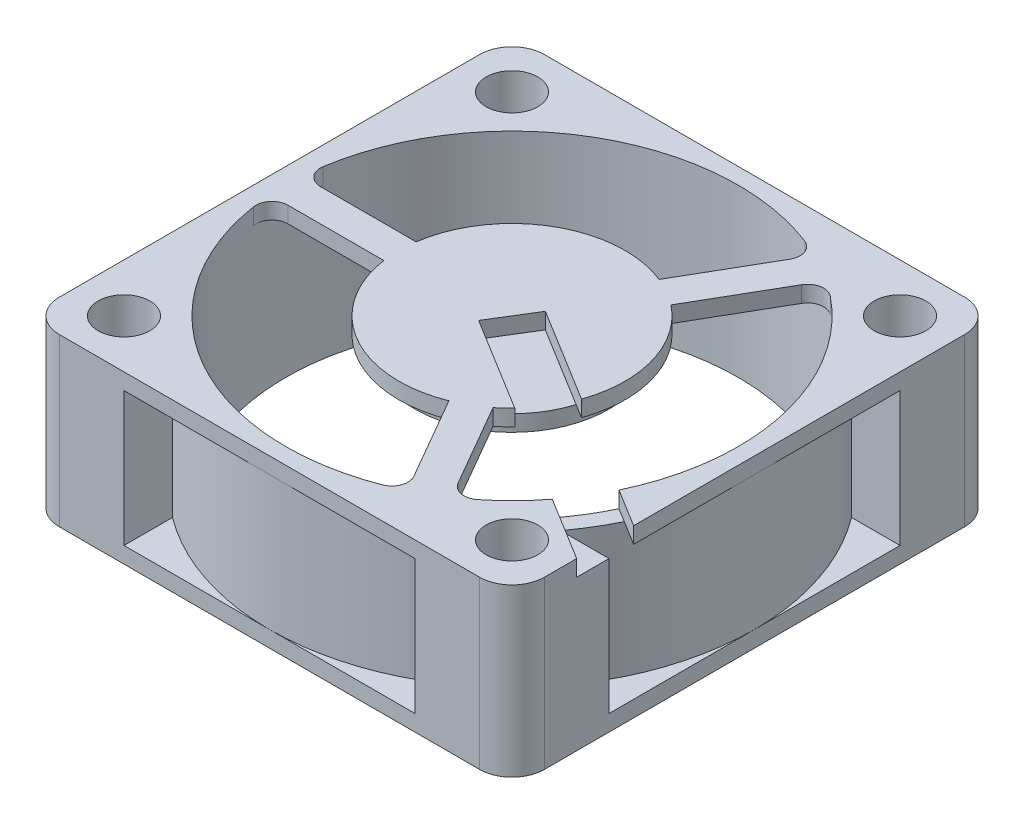
SolidWorks part; units mm, degrees
ref_plane "Alzado" through (0, 0, 0) normal (0, 0, 1) x (1, 0, 0)
ref_plane "Planta" through (0, 0, 0) normal (0, 1, 0) x (1, 0, 0)
ref_plane "Vista lateral" through (0, 0, 0) normal (1, 0, 0) x (0, 0, -1)
sketch "Croquis2" plane through (0, 0, 0) normal (0, 1, 0) x (1, 0, 0)
  line L0 (-14, 14) -> (14, 14)
  line L1 (-15, -15) -> (15, -15)
  line L2 (-15, -15) -> (-15, 15)
  line L3 (-15, 15) -> (15, 15)
  line L4 (15, -15) -> (15, 15)
  line L5 (-15, -15) -> (15, 15) construction
  line L6 (-15, 15) -> (15, -15) construction
  line L7 (14, -14) -> (14, 14)
  line L8 (-14, -14) -> (14, -14)
  line L9 (-14, -14) -> (-14, 14)
  line L10 (9.1857, -12) -> (9.1857, -14)
  line L11 (12, -9.1857) -> (14, -9.1857)
  line L12 (9.6143, 12) -> (9.6143, 14)
  line L13 (12, 9.6143) -> (15, 9.6143)
  line L14 (-9.1857, 12) -> (-9.1857, 14)
  line L15 (-12, 9.1857) -> (-14, 9.1857)
  line L16 (-12, -9.1857) -> (-14, -9.1857)
  line L17 (-9.1857, -12) -> (-9.1857, -14)
  circle A0 centre (-12, 12) radius 1.6
  circle A1 centre (12, 12) radius 1.6
  circle A2 centre (12, -12) radius 1.6
  circle A3 centre (-12, -12) radius 1.6
  circle A4 centre (-12, 12) radius 2.8143
  circle A5 centre (12, 12) radius 2.3857
  circle A6 centre (12, -12) radius 2.8143
  circle A7 centre (-12, -12) radius 2.8143
  circle A8 centre (0, 0) radius 14
  point P0 (0, 0)
  dimension "D3" = 3.2
  dimension "D1" = 30
  dimension "D2" = 30
  dimension "D4" = 24
  dimension "D5" = 24
  dimension "D6" = 1
extrude "Saliente-Extruir1" add sketch "Croquis2" along normal blind 1 contours A7 L9 A4 L0 A5 L7 L4 L3 L2 L1 A6 L8 | L7 A5 | L7 A5 L0 A1 | A5 L13 L7 | L0 A5 | A5 L7 L0 | A5 L0 L12 | L9 A4 | L0 A4 | L0 A4 L9 A0 | A4 L14 L0 | A4 L9 L15 | L8 A7 | L9 A7 | L8 A7 L9 A3 | A7 L16 L9 | A7 L8 L17 | A8 L9 L16 A7 L17 L8 | A8 L8 L10 A6 L11 L7 | A8 L7 L13 A5 L12 L0 | A8 L0 L14 A4 L15 L9 | L8 A6 | L7 A6 | A6 L7 L11 | A6 L10 L8 | L8 A6 L7 A2 region at (14.5757, 0, 2.6929) region at (-12, 0, -14.3301) region at (-12, 0, -13.9319) region at (-14.3301, 0, -12) region at (-9.4281, 0, -13.516) region at (-13.516, 0, -9.4281) region at (-9.9747, 0, -9.9747) region at (10.0887, 0, -10.0887) region at (-9.9747, 0, 9.9747) region at (9.9215, 0, -13.5255) region at (9.9747, 0, 9.9747) region at (-13.516, 0, 9.4281) region at (12, 0, -14.1554) region at (12, 0, -13.938) region at (13.516, 0, 9.4281) region at (13.5255, 0, -9.9215) region at (-13.0573, 0, 9.4655) region at (-14.3301, 0, 12) region at (-9.4281, 0, 13.516) region at (9.4281, 0, 13.516) region at (13.7835, 0, -13.7835) region at (14.3301, 0, 12) region at (13.9319, 0, 12) region at (14.1554, 0, -12) region at (-12, 0, 14.3301) region at (12, 0, 14.3301)
sketch "Croquis3" plane through (0, 1, 0) normal (0, 1, 0) x (1, 0, 0)
  line L0 (-15, -15) -> (-15, 15) construction
  circle A0 centre (0, 0) radius 14
  circle A1 centre (0, 0) radius 15
  dimension "D1" = 1
extrude "Saliente-Extruir2" add sketch "Croquis3" against normal blind 10.3
sketch "Croquis5" plane through (0, 1, 0) normal (0, 1, 0) x (1, 0, 0)
  line L0 (-15, -1) -> (15, -1)
  line L1 (-15, -15) -> (-15, 15) construction
  line L2 (-15, -1) -> (-15, 1)
  line L3 (15, -15) -> (15, 15) construction
  line L4 (15, -1) -> (15, 1)
  line L5 (15, 1) -> (-15, 1)
  line L6 (6.634, 13.4904) -> (-8.366, -12.4904)
  line L7 (-6.634, -13.4904) -> (8.366, 12.4904)
  line L8 (8.366, -12.4904) -> (-6.634, 13.4904)
  line L9 (-8.366, 12.4904) -> (6.634, -13.4904)
  line L10 (8.366, 12.4904) -> (6.634, 13.4904)
  line L11 (-6.634, 13.4904) -> (-8.366, 12.4904)
  line L12 (-6.634, -13.4904) -> (-8.366, -12.4904)
  line L13 (8.366, -12.4904) -> (6.634, -13.4904)
  circle A0 centre (0, 0) radius 7
  point P22 (0, 0)
  dimension "D1" = 14
  dimension "D2" = 2
  dimension "D3" = 1
  dimension "D4" = 3
extrude "Saliente-Extruir4" add sketch "Croquis5" against normal blind 1 contours A0 L5 L0 | L5 A0 L0 L6 L9 | L9 A0 L5 | L8 A0 L9 L5 L6 | L6 A0 L8 | L5 A0 L7 | L7 A0 L6 L8 L5 | L0 A0 L5 L7 L8 | L8 A0 L0 | L9 A0 L8 L0 L7 | L7 A0 L9 | L6 A0 L7 L9 L0 | L0 A0 L6 | L6 L9 L0 L7 L8 L5 | L5 L9 L6 | L9 L6 L0 | L0 L9 L7 | L0 L8 L7 | L8 L7 L5 | L5 L8 L6 | A0 L7 L6 | A0 L9 L8 region at (-10.988, 1, 0) region at (-4.2073, 1, 0) region at (-4.5214, 1, 2.6104) region at (-1.1547, 1, 0.6667) region at (-2.1036, 1, 3.6436) region at (-4.5214, 1, -2.6104) region at (0, 1, 0) region at (0, 1, 1.3333) region at (-1.1547, 1, -0.6667) region at (-2.1036, 1, -3.6436) region at (0, 1, 5.2208) region at (1.1547, 1, 0.6667) region at (2.1036, 1, 3.6436) region at (0, 1, -1.3333) region at (0, 1, -5.2208) region at (5.494, 1, 9.5159) region at (4.2073, 1, 0) region at (4.5214, 1, 2.6104) region at (1.1547, 1, -0.6667) region at (2.1036, 1, -3.6436) region at (5.494, 1, -9.5159) region at (4.5214, 1, -2.6104)
fillet "Redondeo2" radius 1 6 edges at (6.1161, 0.5, -12.5934) (7.8481, 0.5, -11.5934) (-13.9642, 0.5, -1) (-13.9642, 0.5, 1) (6.1161, 0.5, 12.5934) (7.8481, 0.5, 11.5934)
fillet "Redondeo3" radius 2 4 edges at (15, 0.5, 15) (15, 0.5, -15) (-15, 0.5, 15) (-15, 0.5, -15)
sketch "Croquis11" plane through (0, -9.3, 0) normal (0, -1, 0) x (1, 0, 0)
  line L2 (15, 0) -> (15, 13)
  line L3 (13, 15) -> (0, 15)
  line L4 (15, 0) -> (15, 13)
  line L5 (13, 15) -> (0, 15)
  line L6 (0, 15) -> (-13, 15)
  line L7 (-15, 13) -> (-15, 0)
  line L8 (0, 15) -> (-13, 15)
  line L9 (-15, 13) -> (-15, 0)
  line L10 (-15, 0) -> (-15, -13)
  line L11 (-13, -15) -> (0, -15)
  line L12 (-15, 0) -> (-15, -13)
  line L13 (-13, -15) -> (0, -15)
  line L14 (0, -15) -> (13, -15)
  line L15 (15, -13) -> (15, 0)
  line L16 (0, -15) -> (13, -15)
  line L17 (15, -13) -> (15, 0)
  circle A0 centre (-12, -12) radius 1.6 construction
  circle A1 centre (12, -12) radius 1.6 construction
  arc A2 (15, 13) -> (13, 15) centre (13, 13) ccw
  arc A3 (15, 0) -> (0, 15) centre (0, 0) ccw
  arc A4 (15, 13) -> (13, 15) centre (13, 13) ccw
  arc A5 (15, 0) -> (0, 15) centre (0, 0) ccw
  arc A6 (-13, 15) -> (-15, 13) centre (-13, 13) ccw
  arc A7 (0, 15) -> (-15, 0) centre (0, 0) ccw
  arc A8 (-13, 15) -> (-15, 13) centre (-13, 13) ccw
  arc A9 (0, 15) -> (-15, 0) centre (0, 0) ccw
  arc A10 (-15, -13) -> (-13, -15) centre (-13, -13) ccw
  arc A11 (-15, 0) -> (0, -15) centre (0, 0) ccw
  arc A12 (-15, -13) -> (-13, -15) centre (-13, -13) ccw
  arc A13 (-15, 0) -> (0, -15) centre (0, 0) ccw
  arc A14 (13, -15) -> (15, -13) centre (13, -13) ccw
  arc A15 (0, -15) -> (15, 0) centre (0, 0) ccw
  arc A16 (13, -15) -> (15, -13) centre (13, -13) ccw
  arc A17 (0, -15) -> (15, 0) centre (0, 0) ccw
  circle A18 centre (12, 12) radius 1.6 construction
  circle A19 centre (-12, 12) radius 1.6 construction
  circle A20 centre (-12, -12) radius 1.6
  circle A21 centre (12, -12) radius 1.6
  circle A22 centre (12, 12) radius 1.6
  circle A23 centre (-12, 12) radius 1.6
  circle M18 centre (0, 0) radius 15
  dimension "D1" = 0
  dimension "D2" = 0
  dimension "D3" = 0
  dimension "D4" = 0
extrude "Saliente-Extruir9" add sketch "Croquis11" against normal blind 1 contours L8 A8 L9 A23 M18 | L4 A4 L5 A22 M18 | L16 A16 L17 A21 M18 | L12 A12 L13 A20 M18 region at (10.7566, -9.3, 10.7566) region at (14.7879, -9.3, -6.5) region at (-10.7566, -9.3, 10.7566) region at (-6.5, -9.3, -14.7879)
sketch "Croquis12" plane through (0, 0, 0) normal (0, -1, 0) x (1, 0, 0)
  line L0 (-15, 13) -> (-15, -13) construction
  line L1 (-15, -9) -> (-15, -13)
  line L2 (-13, -15) -> (13, -15) construction
  line L3 (-13, -15) -> (-9, -15)
  line L4 (-9, -12) -> (-9, -15)
  line L5 (-12, -9) -> (-15, -9)
  line L6 (-9, -12) -> (-9, -10.7238)
  line L7 (-12, -9) -> (-10.7238, -9)
  line L8 (0, 0) -> (0, 15) construction
  line L9 (13, 15) -> (-13, 15) construction
  line L10 (0, 0) -> (15, 0) construction
  line L11 (15, -13) -> (15, 13) construction
  line L12 (12, -9) -> (10.7238, -9)
  line L13 (9, -12) -> (9, -10.7238)
  line L14 (12, -9) -> (15, -9)
  line L15 (9, -12) -> (9, -15)
  line L16 (13, -15) -> (9, -15)
  line L17 (15, -9) -> (15, -13)
  line L18 (15, 9) -> (15, 13)
  line L19 (13, 15) -> (9, 15)
  line L20 (9, 12) -> (9, 15)
  line L21 (12, 9) -> (15, 9)
  line L22 (9, 12) -> (9, 10.7238)
  line L23 (12, 9) -> (10.7238, 9)
  line L24 (-12, 9) -> (-10.7238, 9)
  line L25 (-9, 12) -> (-9, 10.7238)
  line L26 (-12, 9) -> (-15, 9)
  line L27 (-9, 12) -> (-9, 15)
  line L28 (-13, 15) -> (-9, 15)
  line L29 (-15, 9) -> (-15, 13)
  circle A0 centre (-12, -12) radius 3
  arc A1 (-15, -13) -> (-13, -15) centre (-13, -13) ccw construction
  arc A2 (-15, -13) -> (-13, -15) centre (-13, -13) ccw
  circle A3 centre (0, 0) radius 14 construction
  arc A4 (-10.7238, -9) -> (-9, -10.7238) centre (0, 0) ccw
  circle A5 centre (-12, -12) radius 1.6 construction
  circle A6 centre (-12, -12) radius 1.6
  circle A7 centre (12, -12) radius 1.6
  arc A8 (10.7238, -9) -> (9, -10.7238) centre (0, 0) cw
  arc A9 (15, -13) -> (13, -15) centre (13, -13) cw
  circle A10 centre (12, -12) radius 3
  circle A11 centre (12, 12) radius 3
  arc A12 (15, 13) -> (13, 15) centre (13, 13) ccw
  arc A13 (10.7238, 9) -> (9, 10.7238) centre (0, 0) ccw
  circle A14 centre (12, 12) radius 1.6
  circle A15 centre (-12, 12) radius 1.6
  arc A16 (-10.7238, 9) -> (-9, 10.7238) centre (0, 0) cw
  arc A17 (-15, 13) -> (-13, 15) centre (-13, 13) cw
  circle A18 centre (-12, 12) radius 3
  circle M4 centre (-12, -12) radius 1.6
  arc M5 (-14, -13.98) -> (-13.98, -14) centre (-12, -12) ccw
  line M6 (-13.98, -14) -> (-14, -14)
  line M7 (-14, -14) -> (-14, -13.98)
  line M8 (-15, 0) -> (-15, -13)
  arc M9 (-15, -13) -> (-13, -15) centre (-13, -13) ccw
  line M10 (-13, -15) -> (0, -15)
  arc M11 (0, -15) -> (-15, 0) centre (0, 0) cw
extrude "Saliente-Extruir10" add sketch "Croquis12" along normal up to surface (8.3 mm away) contours A0 L3 L4 | A4 A0 M11 | L16 A10 L15 | L17 A10 L16 A9 | L14 A10 L17 | A10 A8 A7 | L13 A10 A8 | A8 A10 L12 | A16 A18 L24 | L25 A18 A16 | A18 A16 A15 | L26 A18 L29 | L29 A18 L28 A17 | L28 A18 L27 | A13 L23 A11 | A13 A11 L22 | A13 A11 A14 | L18 A12 L19 A11 | A11 L21 L18 | A11 L19 L20 | A0 M11 M7 M5 M6 M4 | A0 L5 M8 | A0 L1 M9 M10 | A4 L7 A0 | A4 A0 L6 region at (-14.3299, 0, -9.6701) region at (-14.1512, 0, -14.1512) region at (-14.0613, 0, -9.9387) region at (-10.8623, 0, -9.1584) region at (-10.292, 0, -10.292) region at (-9.6701, 0, -14.3299) region at (-9.1584, 0, -10.8623) region at (10.8623, 0, -9.1584) region at (14.3299, 0, -9.6701) region at (14.0613, 0, -9.9387) region at (14.1512, 0, -14.1512) region at (9.6701, 0, -14.3299) region at (9.1584, 0, -10.8623) region at (14.3299, 0, 9.6701) region at (14.1512, 0, 14.1512) region at (14.0613, 0, 9.9387) region at (10.8623, 0, 9.1584) region at (9.6701, 0, 14.3299) region at (9.1584, 0, 10.8623) region at (-10.8623, 0, 9.1584) region at (-14.3299, 0, 9.6701) region at (-14.0613, 0, 9.9387) region at (-14.1512, 0, 14.1512) region at (-9.6701, 0, 14.3299) region at (-9.1584, 0, 10.8623) up to face at (-12, -8.3, -13.6)
sketch "Croquis13" plane through (0, 0, 0) normal (0, -1, 0) x (1, 0, 0)
  circle A0 centre (0, 0) radius 6
  dimension "D1" = 12
extrude "Saliente-Extruir11" add sketch "Croquis13" along normal blind 1
sketch "Croquis14" plane through (0, 1, 0) normal (0, 1, 0) x (1, 0, 0)
  line L0 (15, -11) -> (-0.7866, -1.2772)
  line L1 (-0.7866, -1.2772) -> (0.7866, 1.2772)
  line L2 (0.7866, 1.2772) -> (16.5732, -8.4456)
  line L3 (16.5732, -8.4456) -> (15, -11)
  line L4 (15, -13) -> (15, 13) construction
  line L5 (-13, -15) -> (13, -15) construction
  dimension "D1" = 3
  dimension "D2" = 4
  dimension "D3" = 90
extrude "Cortar-Extruir1" cut sketch "Croquis14" against normal blind 1
